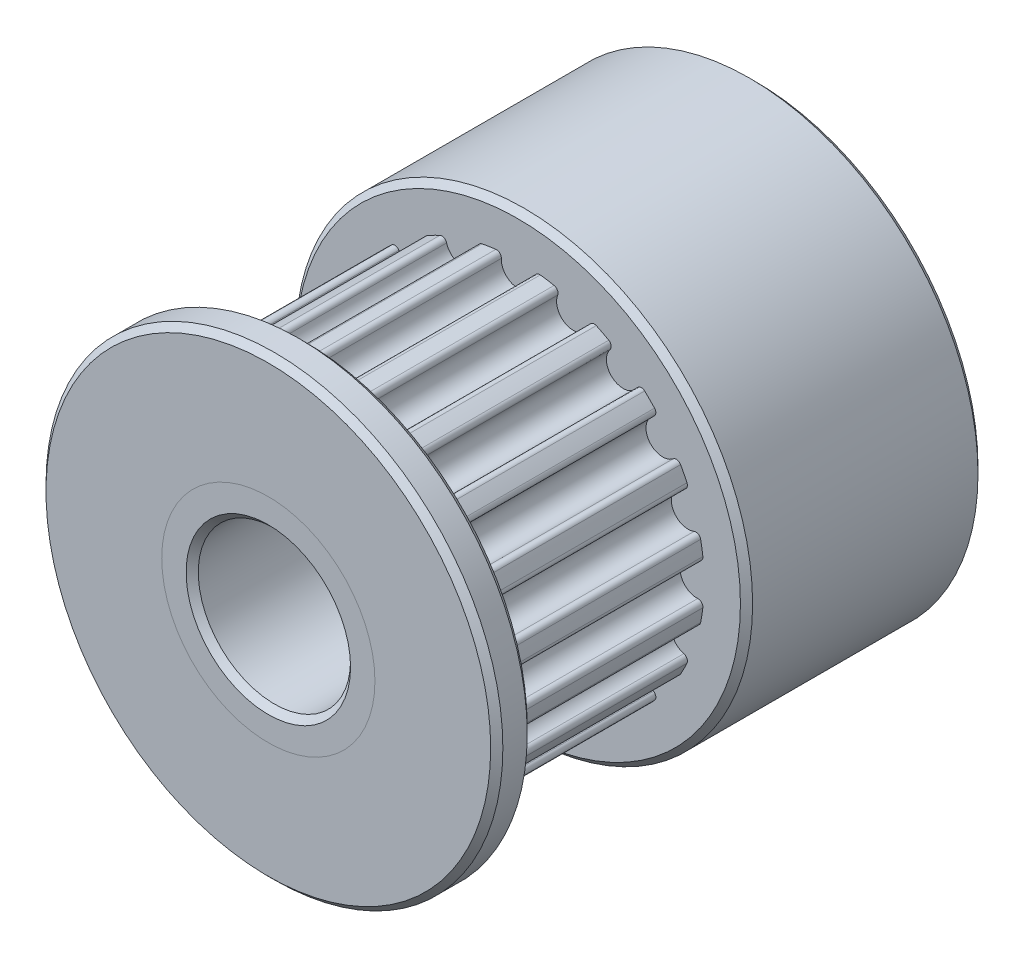
SolidWorks part; units mm, degrees
ref_plane "Přední rovina" through (0, 0, 0) normal (0, 0, 1) x (1, 0, 0)
ref_plane "Horní rovina" through (0, 0, 0) normal (0, 1, 0) x (1, 0, 0)
ref_plane "Pravá rovina" through (0, 0, 0) normal (1, 0, 0) x (0, 0, -1)
sketch "Skica1" plane through (0, 0, 0) normal (0, 0, 1) x (1, 0, 0)
  circle A100 centre (0, 0) radius 2.5
  circle A102 centre (0, 0) radius 3.5
  circle A104 centre (0, 0) radius 7.5
  arc A105 (-0.5492, 5.8991) -> (0.5492, 5.8991) centre (0, 5.87) ccw
  arc A106 (-0.5492, 5.8991) -> (-0.7281, 6.0665) centre (-0.709, 5.9076) ccw
  arc A107 (0.7281, 6.0665) -> (0.5492, 5.8991) centre (0.709, 5.9076) ccw
  arc A108 (1.1822, 5.9945) -> (0.7281, 6.0665) centre (0, 0) ccw
  arc A109 (1.3006, 5.7801) -> (2.3453, 5.4407) centre (1.8139, 5.5827) ccw
  arc A110 (1.3006, 5.7801) -> (1.1822, 5.9945) centre (1.1512, 5.8376) ccw
  arc A111 (2.5671, 5.5446) -> (2.3453, 5.4407) centre (2.4999, 5.3994) ccw
  arc A112 (2.9768, 5.3358) -> (2.5671, 5.5446) centre (0, 0) ccw
  arc A113 (3.0231, 5.0953) -> (3.9118, 4.4497) centre (3.4503, 4.7489) ccw
  arc A114 (3.0231, 5.0953) -> (2.9768, 5.3358) centre (2.8988, 5.1961) ccw
  arc A115 (4.1548, 4.4799) -> (3.9118, 4.4497) centre (4.046, 4.3626) ccw
  arc A116 (4.4799, 4.1548) -> (4.1548, 4.4799) centre (0, 0) ccw
  arc A117 (4.4497, 3.9118) -> (5.0953, 3.0231) centre (4.7489, 3.4503) ccw
  arc A118 (4.4497, 3.9118) -> (4.4799, 4.1548) centre (4.3626, 4.046) ccw
  arc A119 (5.3358, 2.9768) -> (5.0953, 3.0231) centre (5.1961, 2.8988) ccw
  arc A120 (5.5446, 2.5671) -> (5.3358, 2.9768) centre (0, 0) ccw
  arc A121 (5.4407, 2.3453) -> (5.7801, 1.3006) centre (5.5827, 1.8139) ccw
  arc A122 (5.4407, 2.3453) -> (5.5446, 2.5671) centre (5.3994, 2.4999) ccw
  arc A123 (5.9945, 1.1822) -> (5.7801, 1.3006) centre (5.8376, 1.1512) ccw
  arc A124 (6.0665, 0.7281) -> (5.9945, 1.1822) centre (0, 0) ccw
  arc A125 (5.8991, 0.5492) -> (5.8991, -0.5492) centre (5.87, 0) ccw
  arc A126 (5.8991, 0.5492) -> (6.0665, 0.7281) centre (5.9076, 0.709) ccw
  arc A127 (6.0665, -0.7281) -> (5.8991, -0.5492) centre (5.9076, -0.709) ccw
  arc A128 (5.9945, -1.1822) -> (6.0665, -0.7281) centre (0, 0) ccw
  arc A129 (5.7801, -1.3006) -> (5.4407, -2.3453) centre (5.5827, -1.8139) ccw
  arc A130 (5.7801, -1.3006) -> (5.9945, -1.1822) centre (5.8376, -1.1512) ccw
  arc A131 (5.5446, -2.5671) -> (5.4407, -2.3453) centre (5.3994, -2.4999) ccw
  arc A132 (5.3358, -2.9768) -> (5.5446, -2.5671) centre (0, 0) ccw
  arc A133 (5.0953, -3.0231) -> (4.4497, -3.9118) centre (4.7489, -3.4503) ccw
  arc A134 (5.0953, -3.0231) -> (5.3358, -2.9768) centre (5.1961, -2.8988) ccw
  arc A135 (4.4799, -4.1548) -> (4.4497, -3.9118) centre (4.3626, -4.046) ccw
  arc A136 (4.1548, -4.4799) -> (4.4799, -4.1548) centre (0, 0) ccw
  arc A137 (3.9118, -4.4497) -> (3.0231, -5.0953) centre (3.4503, -4.7489) ccw
  arc A138 (3.9118, -4.4497) -> (4.1548, -4.4799) centre (4.046, -4.3626) ccw
  arc A139 (2.9768, -5.3358) -> (3.0231, -5.0953) centre (2.8988, -5.1961) ccw
  arc A140 (2.5671, -5.5446) -> (2.9768, -5.3358) centre (0, 0) ccw
  arc A141 (2.3453, -5.4407) -> (1.3006, -5.7801) centre (1.8139, -5.5827) ccw
  arc A142 (2.3453, -5.4407) -> (2.5671, -5.5446) centre (2.4999, -5.3994) ccw
  arc A143 (1.1822, -5.9945) -> (1.3006, -5.7801) centre (1.1512, -5.8376) ccw
  arc A144 (0.7281, -6.0665) -> (1.1822, -5.9945) centre (0, 0) ccw
  arc A145 (0.5492, -5.8991) -> (-0.5492, -5.8991) centre (0, -5.87) ccw
  arc A146 (0.5492, -5.8991) -> (0.7281, -6.0665) centre (0.709, -5.9076) ccw
  arc A147 (-0.7281, -6.0665) -> (-0.5492, -5.8991) centre (-0.709, -5.9076) ccw
  arc A148 (-1.1822, -5.9945) -> (-0.7281, -6.0665) centre (0, 0) ccw
  arc A149 (-1.3006, -5.7801) -> (-2.3453, -5.4407) centre (-1.8139, -5.5827) ccw
  arc A150 (-1.3006, -5.7801) -> (-1.1822, -5.9945) centre (-1.1512, -5.8376) ccw
  arc A151 (-2.5671, -5.5446) -> (-2.3453, -5.4407) centre (-2.4999, -5.3994) ccw
  arc A152 (-2.9768, -5.3358) -> (-2.5671, -5.5446) centre (0, 0) ccw
  arc A153 (-3.0231, -5.0953) -> (-3.9118, -4.4497) centre (-3.4503, -4.7489) ccw
  arc A154 (-3.0231, -5.0953) -> (-2.9768, -5.3358) centre (-2.8988, -5.1961) ccw
  arc A155 (-4.1548, -4.4799) -> (-3.9118, -4.4497) centre (-4.046, -4.3626) ccw
  arc A156 (-4.4799, -4.1548) -> (-4.1548, -4.4799) centre (0, 0) ccw
  arc A157 (-4.4497, -3.9118) -> (-5.0953, -3.0231) centre (-4.7489, -3.4503) ccw
  arc A158 (-4.4497, -3.9118) -> (-4.4799, -4.1548) centre (-4.3626, -4.046) ccw
  arc A159 (-5.3358, -2.9768) -> (-5.0953, -3.0231) centre (-5.1961, -2.8988) ccw
  arc A160 (-5.5446, -2.5671) -> (-5.3358, -2.9768) centre (0, 0) ccw
  arc A161 (-5.4407, -2.3453) -> (-5.7801, -1.3006) centre (-5.5827, -1.8139) ccw
  arc A162 (-5.4407, -2.3453) -> (-5.5446, -2.5671) centre (-5.3994, -2.4999) ccw
  arc A163 (-5.9945, -1.1822) -> (-5.7801, -1.3006) centre (-5.8376, -1.1512) ccw
  arc A164 (-6.0665, -0.7281) -> (-5.9945, -1.1822) centre (0, 0) ccw
  arc A165 (-5.8991, -0.5492) -> (-5.8991, 0.5492) centre (-5.87, 0) ccw
  arc A166 (-5.8991, -0.5492) -> (-6.0665, -0.7281) centre (-5.9076, -0.709) ccw
  arc A167 (-6.0665, 0.7281) -> (-5.8991, 0.5492) centre (-5.9076, 0.709) ccw
  arc A168 (-5.9945, 1.1822) -> (-6.0665, 0.7281) centre (0, 0) ccw
  arc A169 (-5.7801, 1.3006) -> (-5.4407, 2.3453) centre (-5.5827, 1.8139) ccw
  arc A170 (-5.7801, 1.3006) -> (-5.9945, 1.1822) centre (-5.8376, 1.1512) ccw
  arc A171 (-5.5446, 2.5671) -> (-5.4407, 2.3453) centre (-5.3994, 2.4999) ccw
  arc A172 (-5.3358, 2.9768) -> (-5.5446, 2.5671) centre (0, 0) ccw
  arc A173 (-5.0953, 3.0231) -> (-4.4497, 3.9118) centre (-4.7489, 3.4503) ccw
  arc A174 (-5.0953, 3.0231) -> (-5.3358, 2.9768) centre (-5.1961, 2.8988) ccw
  arc A175 (-4.4799, 4.1548) -> (-4.4497, 3.9118) centre (-4.3626, 4.046) ccw
  arc A176 (-4.1548, 4.4799) -> (-4.4799, 4.1548) centre (0, 0) ccw
  arc A177 (-3.9118, 4.4497) -> (-3.0231, 5.0953) centre (-3.4503, 4.7489) ccw
  arc A178 (-3.9118, 4.4497) -> (-4.1548, 4.4799) centre (-4.046, 4.3626) ccw
  arc A179 (-2.9768, 5.3358) -> (-3.0231, 5.0953) centre (-2.8988, 5.1961) ccw
  arc A180 (-2.5671, 5.5446) -> (-2.9768, 5.3358) centre (0, 0) ccw
  arc A181 (-2.3453, 5.4407) -> (-1.3006, 5.7801) centre (-1.8139, 5.5827) ccw
  arc A182 (-2.3453, 5.4407) -> (-2.5671, 5.5446) centre (-2.4999, 5.3994) ccw
  arc A183 (-1.1822, 5.9945) -> (-1.3006, 5.7801) centre (-1.1512, 5.8376) ccw
  arc A184 (-0.7281, 6.0665) -> (-1.1822, 5.9945) centre (0, 0) ccw
  point P226 (0, 0)
  point P366 (0, 0)
  dimension "D1" = 7
  dimension "D2" = 15
  dimension "D3" = 5
extrude "Přidat vysunutím1" add sketch "Skica1" against normal blind 7.8 contours A102 A100 region at (-3.401, 0, 0)
extrude "Přidat vysunutím3" add sketch "Skica1<4>" against normal blind 7.8 contours A106 A184 A183 A181 A182 A180 A179 A177 A178 A176 A175 A173 A174 A172 A171 A169 A170 A168 A167 A165 A166 A164 A163 A161 A162 A160 A159 A157 A158 A156 A155 A153 A154 A152 A151 A149 A150 A148 A147 A145 A146 A144 A143 A141 A142 A140 A139 A137 A138 A136 A135 | A104 A184 A106 A105 A107 A108 A110 A109 A111 A112 A114 A113 A115 A116 A118 A117 A119 A120 A122 A121 A123 A124 A126 A125 A127 A128 A130 A129 A131 A132 A134 A133 A135 A136 A138 A137 A139 A140 A142 A141 A143 A144 A146 A145 A147 A148 A150 A149 A151 A152 region at (-7.2879, 0, 0) region at (0, 5.1484, 0)
sketch "Skica1<4>" plane through (0, 0, 0) normal (0, 0, 1) x (1, 0, 0) same geometry as "Skica1"
sketch "Skica4" plane through (0, 0, 0) normal (1, 0, 0) x (0, 0, -1)
  circle A0 centre (3.9, 0) radius 1.65
  dimension "D1" = 3.9
  dimension "D2" = 3.3
sketch "Skica3" plane through (0, 0, 0) normal (0, 1, 0) x (1, 0, 0)
  circle A0 centre (0, 3.9) radius 1.65
  dimension "D1" = 3.9
  dimension "D2" = 3.3
extrude "Odebrat vysunutím1" cut sketch "Skica4" against normal blind 8
extrude "Odebrat vysunutím2" cut sketch "Skica3" against normal blind 8
extrude "Přidat vysunutím4" add sketch "Skica1<7>" along normal blind 8.2 separate body contours A102 A100 region at (-3.401, 0, 0)
sketch "Skica1<7>" plane through (0, 0, 0) normal (0, 0, 1) x (1, 0, 0) same geometry as "Skica1"
extrude "Přidat vysunutím5" add sketch "Skica1<8>" along normal blind 7 contours A106 A184 A183 A181 A182 A180 A179 A177 A178 A176 A175 A173 A174 A172 A171 A169 A170 A168 A167 A165 A166 A164 A163 A161 A162 A160 A159 A157 A158 A156 A155 A153 A154 A152 A151 A149 A150 A148 A147 A145 A146 A144 A143 A141 A142 A140 A139 A137 A138 A136 A135 region at (0, 5.1484, 0)
sketch "Skica1<8>" plane through (0, 0, 0) normal (0, 0, 1) x (1, 0, 0) same geometry as "Skica1"
sketch "Skica5" plane through (0, 0, 7) normal (0, 0, 1) x (1, 0, 0)
  circle A0 centre (0, 0) radius 3.5
  circle A1 centre (0, 0) radius 7.5
extrude "Přidat vysunutím6" add sketch "Skica5" along normal blind 1.2 separate body
sketch3d "3DSkica7"
  point P0 (-7.4981, -0.1669, -6.5985)
ref_plane "Rovina7" through (-7.5981, 0, 0) normal (-1, 0, 0) x (0, 0, 1)
sketch3d "3DSkica8"
  point P0 (-0.4655, -7.4855, -6.345)
ref_plane "Rovina8" through (0, -7.5855, 0) normal (0, -1, 0) x (-1, 0, 0)
hole_wizard "Kuželové zahloubení pro M4 šroubu se zápustnou hlavou plochou4" positions "Skica22" profile "Skica23" countersink size "M4" standard "ISO"
sketch "Skica22" plane through (-7.5981, 0, 0) normal (-1, 0, 0) x (0, 0, 1)
  point P0 (-3.9, 0)
sketch "Skica23" plane through (-7.5981, 0, -3.9) normal (0, 1, 0) x (0, 0, 1)
  line L0 (0, 0) -> (0, 7.9914)
  line L1 (0, 7.9914) -> (1.65, 7)
  line L2 (1.65, 7) -> (1.65, 0.85)
  line L3 (1.65, 0.85) -> (2.5, 0)
  line L5 (2.5, 0) -> (0, 0)
  line L6 (-1.65, 0.85) -> (-2.5, 0) construction
  line L10 (0, 7.9914) -> (-1.65, 7) construction
  line L11 (0, -6.35) -> (0, 107.95) construction
  dimension "Průměr díry" = 3.3
  dimension "Hloubka díry" = 7
  dimension "Průměr blíz. kuž. zahloubení" = 5
  dimension "Úhel blíz. kuž. zahloubení" = 90
  dimension "Úhel vrtání" = 118
hole_wizard "Kuželové zahloubení pro M4 šroubu se zápustnou hlavou plochou5" positions "Skica24" profile "Skica25" countersink size "M4" standard "ISO"
sketch "Skica24" plane through (0, -7.5855, 0) normal (0, -1, 0) x (-1, 0, 0)
  point P0 (0, 3.9)
sketch "Skica25" plane through (0, -7.5855, -3.9) normal (1, 0, 0) x (0, 0, -1)
  line L0 (0, 0) -> (0, 7.9914)
  line L1 (0, 7.9914) -> (1.65, 7)
  line L2 (1.65, 7) -> (1.65, 0.85)
  line L3 (1.65, 0.85) -> (2.5, 0)
  line L5 (2.5, 0) -> (0, 0)
  line L6 (-1.65, 0.85) -> (-2.5, 0) construction
  line L10 (0, 7.9914) -> (-1.65, 7) construction
  line L11 (0, -6.35) -> (0, 107.95) construction
  dimension "Průměr díry" = 3.3
  dimension "Hloubka díry" = 7
  dimension "Průměr blíz. kuž. zahloubení" = 5
  dimension "Úhel blíz. kuž. zahloubení" = 90
  dimension "Úhel vrtání" = 118
thread "Závit3" pitch 0.7 method cut profile "Profil závitu3" start angle 0, offset 0, length 7, pitch 0.7, diameter 3.3
ref_plane "Rovina9" through (1.65, -7.5855, -3.9) normal (0, 0, 1) x (1, 0, 0)
sketch "Profil závitu3" plane through (1.65, -7.5855, -3.9) normal (0, 0, 1) x (1, 0, 0)
  line L0 (0, 0) -> (0, 0.7) construction
  line L1 (0, 0) -> (0.3789, 0.2187)
  line L2 (0.3789, 0.2187) -> (0.3789, 0.3062)
  line L3 (0.3789, 0.3062) -> (0, 0.525)
  line L4 (0.3789, 0.2625) -> (0, 0.2625) construction
  line L11 (0, 0) -> (0, 0.525)
  point P2 (0, 0)
  dimension "Pitch" = 0.7
  dimension "Profile_Angle" = 60
  dimension "Profile_Land" = 0.0875
  dimension "Profile_Height" = 0.3789
thread "Závit4" pitch 0.7 method cut profile "Profil závitu4" start angle 0, offset 0, length 7, pitch 0.7, diameter 3.3
ref_plane "Rovina10" through (-7.5981, 0, -5.55) normal (0, -1, 0) x (0, 0, -1)
sketch "Profil závitu4" plane through (-7.5981, 0, -5.55) normal (0, -1, 0) x (0, 0, -1)
  line L0 (0, 0) -> (0, 0.7) construction
  line L1 (0, 0) -> (0.3789, 0.2187)
  line L2 (0.3789, 0.2187) -> (0.3789, 0.3062)
  line L3 (0.3789, 0.3062) -> (0, 0.525)
  line L4 (0.3789, 0.2625) -> (0, 0.2625) construction
  line L11 (0, 0) -> (0, 0.525)
  point P2 (0, 0)
  dimension "Pitch" = 0.7
  dimension "Profile_Angle" = 60
  dimension "Profile_Land" = 0.0875
  dimension "Profile_Height" = 0.3789
chamfer "Zkosení1" distance 0.2 angle 45 3 edges at (7.5, 0, -7.8) (2.5, 0, -7.8) (7.5, 0, 0)
chamfer "Zkosení2" distance 0.2 angle 45 1 edges at (2.5, 0, 8.2)
chamfer "Zkosení3" distance 0.2 angle 45 2 edges at (7.5, 0, 8.2) (7.5, 0, 7)
